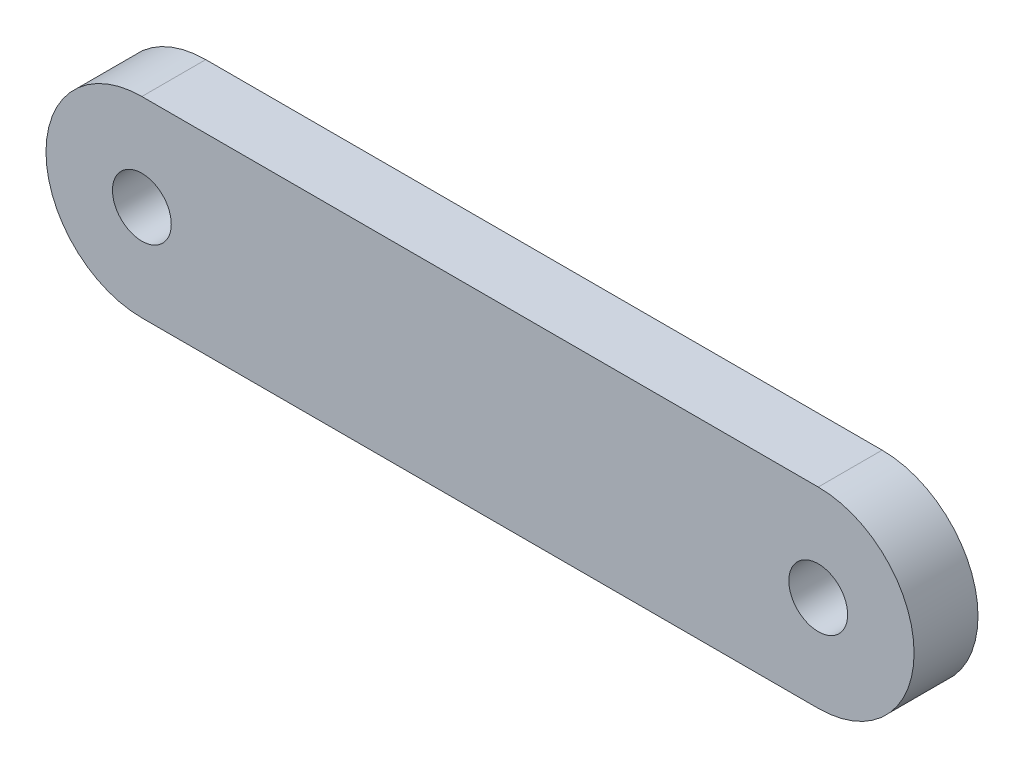
SolidWorks part; units mm, degrees
ref_plane "前视基准面" through (0, 0, 0) normal (0, 0, 1) x (1, 0, 0)
ref_plane "上视基准面" through (0, 0, 0) normal (0, 1, 0) x (1, 0, 0)
ref_plane "右视基准面" through (0, 0, 0) normal (1, 0, 0) x (0, 0, -1)
other "Configuration Table"
sketch "草图1" plane through (0, 0, 0) normal (0, 0, 1) x (1, 0, 0)
  line L1 (-26.46, 7.5) -> (26.46, 7.5)
  line L3 (-26.46, -7.5) -> (26.46, -7.5)
  line L5 (-26.46, 7.5) -> (26.46, -7.5) construction
  line L6 (-26.46, -7.5) -> (26.46, 7.5) construction
  arc A0 (-26.46, 7.5) -> (-26.46, -7.5) centre (-26.46, 0) ccw
  arc A1 (26.46, 7.5) -> (26.46, -7.5) centre (26.46, 0) cw
  circle A2 centre (-26.46, 0) radius 2.3
  circle A3 centre (26.46, 0) radius 2.3
  point P0 (0, 0)
  dimension "D1" = 4.6
  dimension "D2" = 4.6
  dimension "D3" = 52.92
  dimension "D4" = 15
extrude "凸台-拉伸1" add sketch "草图1" along normal blind 5
equation "\"fi\"=4.6"
equation "\"D1@草图1\"=\"fi\""
equation "\"D2@草图1\"=\"fi\""
equation "\"b0\"= 75.6'ground"
equation "\"b1\"= \"b0\" *1.4/ 2'rocker"
equation "\"D3@草图1\"=\"b1\""
equation "\"width\"=15"
equation "\"D4@草图1\"=\"width\""
equation "\"depth\"=5"
equation "\"D1@凸台-拉伸1\"=\"depth\""
equation "\"b2\"= \"b0\"'coupler"
equation "\"b3\"= \"b0\" / 2'coupler"
equation "\"b4\"= \"b0\" *2'leg"
equation "\"angle\"= 40*pi/180'ground水平夹角"
